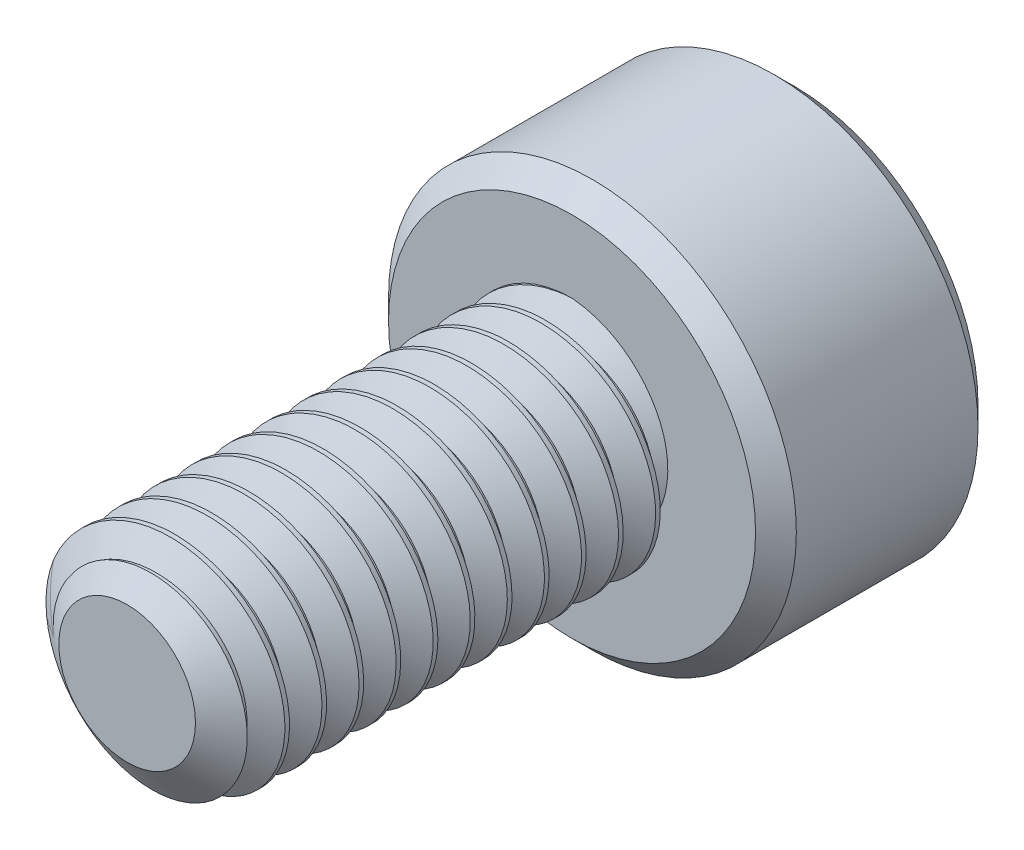
SolidWorks part; units mm, degrees
ref_plane "Front Plane" through (0, 0, 0) normal (0, 0, 1) x (1, 0, 0)
ref_plane "Top Plane" through (0, 0, 0) normal (0, 1, 0) x (1, 0, 0)
ref_plane "Right Plane" through (0, 0, 0) normal (1, 0, 0) x (0, 0, -1)
sketch "Sketch1" plane through (0, 0, 0) normal (0, 0, 1) x (1, 0, 0)
  circle A0 centre (0, 0) radius 1.5
  dimension "OD" = 3
extrude "Extrude1" add sketch "Sketch1" against normal blind 6
sketch "Sketch2" plane through (0, 0, 0) normal (0, 0, 1) x (1, 0, 0)
  circle A0 centre (0, 0) radius 1.5 construction
  circle A1 centre (0, 0) radius 1.5
curve "Helix/Spiral1" pitch 0.5 height 6.5 radius 1.5 centre (0, 0, 0) axis (0, 0, -1) start towards (0, 1, 0) parameters "pitch"=0.5
sketch "Sketch3" plane through (0, 0, 0) normal (1, 0, 0) x (0, 0, -1)
  line L0 (-0.4375, 1.5) -> (-0.25, 1.1752)
  line L1 (-0.25, 1.1752) -> (-0.1875, 1.1752)
  line L2 (-0.1875, 1.1752) -> (0, 1.5)
  line L3 (-0.4375, 1.5) -> (0, 1.5)
  line L4 (-0.2187, 1.5) -> (-0.2187, 1.1752) construction
  line L5 (-0.3437, 1.3376) -> (-0.0937, 1.3376) construction
  line L6 (0, 1.5) -> (0, -1.5) construction
  dimension "D1" = 0.0625
  dimension "D2" = 0.25
  dimension "D3" = 60
sweep "Cut-Sweep1" cut profiles "Sketch3" path "Helix/Spiral1"
sketch "Sketch4" plane through (0, 0, 0) normal (1, 0, 0) x (0, 0, -1)
  line L0 (0.4053, 1.5) -> (0, 0.9212)
  line L1 (0, 0.9212) -> (0, 1.5)
  line L2 (0.4053, 1.5) -> (0, 1.5)
  line L3 (-0.4375, 1.5) -> (0, 1.5) construction
  line L4 (0, 0) -> (7.0209, 0) construction
  dimension "D1" = 55
  dimension "D2" = 0.254
revolve "Cut-Revolve1" cut sketch "Sketch4" angle 360 about L4
sketch "Sketch5" plane through (0, 0, 0) normal (1, 0, 0) x (0, 0, -1)
  line L0 (6, -1.1822) -> (6, 1.0703) construction
  line L1 (6, 1.627) -> (87.4327, 1.627)
  line L2 (6, 1.627) -> (6, 0)
  line L3 (6, 0) -> (87.3125, 0)
  line L4 (87.3125, 1.2968) -> (87.3125, 0)
  line L5 (87.4327, 1.627) -> (87.3125, 1.2968)
  line L6 (0, 0) -> (9.9695, 0) construction
  point P3 (87.3125, 1.627)
  point P10 (87.3125, 1.627)
  dimension "D1" = 0.3302
  dimension "Thread min" = 87.3125
  dimension "D2" = 0.127
  dimension "D3" = 20
revolve "partially thread" [suppressed] add sketch "Sketch5" angle 360 about L6
sketch "Sketch6" plane through (0, 0, -6) normal (0, 0, -1) x (-1, 0, 0)
  circle A0 centre (0, 0) radius 2.75
  dimension "head dia" = 5.5
extrude "Extrude2" add sketch "Sketch6" along normal blind 3
sketch "Sketch7" plane through (0, 0, -9) normal (0, 0, -1) x (-1, 0, 0)
  line L1 (0, 1.4434) -> (-1.25, 0.7217)
  line L2 (-1.25, 0.7217) -> (-1.25, -0.7217)
  line L3 (-1.25, -0.7217) -> (0, -1.4434)
  line L4 (0, -1.4434) -> (1.25, -0.7217)
  line L5 (1.25, -0.7217) -> (1.25, 0.7217)
  line L6 (1.25, 0.7217) -> (0, 1.4434)
  circle A0 centre (0, 0) radius 1.25 construction
  dimension "hex dia" = 2.5
extrude "Cut-Extrude1" cut sketch "Sketch7" against normal blind 1.875
sketch "Sketch8" plane through (0, 0, -9) normal (0, 0, -1) x (-1, 0, 0)
  circle A0 centre (0, 0) radius 1.4434
extrude "Cut-Extrude2" cut sketch "Sketch8" against normal through all draft 45
chamfer "Chamfer1" distance 0.275 angle 45 2 edges at (-2.75, 0, -9) (-2.75, 0, -6)
sketch "Sketch9" plane through (0, 0, 0) normal (1, 0, 0) x (0, 0, -1)
  line L0 (0, 1.5) -> (0, -1.5) construction
  line L1 (2.75, 1.5) -> (2.75, -1.5) construction
  dimension "D1" = 2.75
equation "\"D3@Helix/Spiral1\" = \"screw length@Extrude1\"+\"pitch@Helix/Spiral1\""
equation "\"D1@Sketch3\" = \"pitch@Helix/Spiral1\"*.125"
equation "\"D2@Sketch3\" = \"pitch@Helix/Spiral1\"*.5"
equation "\"D1@Cut-Extrude1\" = \"hex dia@Sketch7\"*.75"
equation "\"D1@Chamfer1\" = \"head dia@Sketch6\"*.05"
equation "\"D1@Sketch9\" = \"pitch@Helix/Spiral1\"*5.5"
